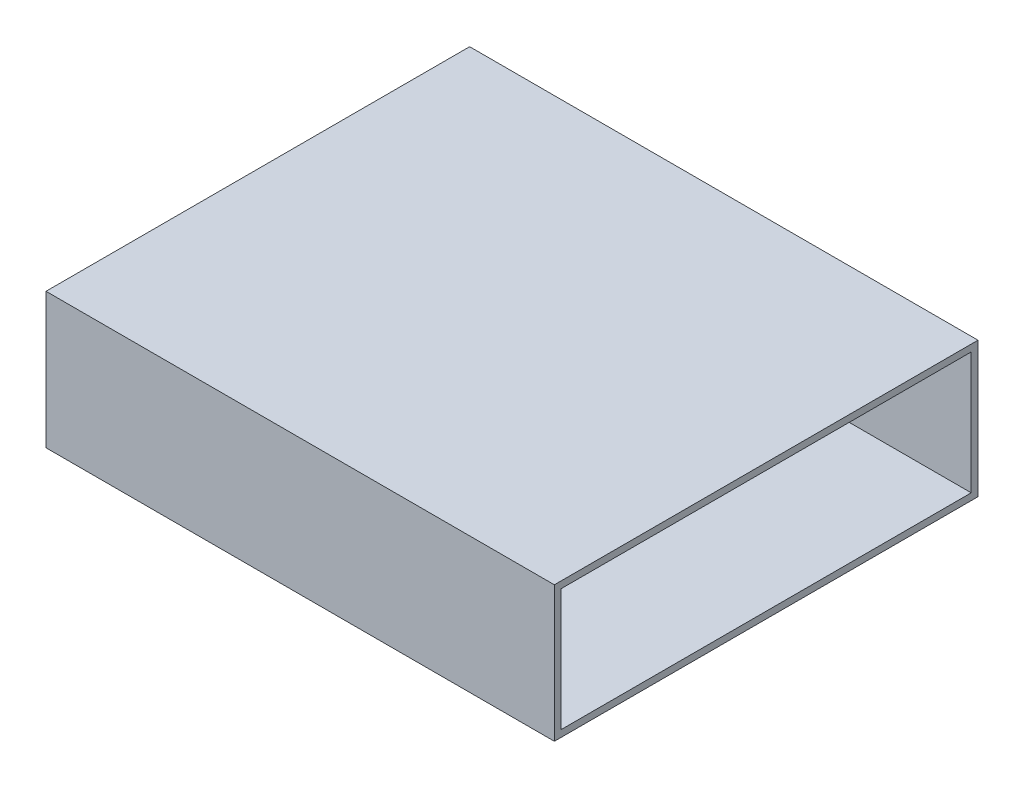
SolidWorks part; units mm, degrees
ref_plane "Front Plane" through (0, 0, 0) normal (0, 0, 1) x (1, 0, 0)
ref_plane "Top Plane" through (0, 0, 0) normal (0, 1, 0) x (1, 0, 0)
ref_plane "Right Plane" through (0, 0, 0) normal (1, 0, 0) x (0, 0, -1)
sketch "Sketch1" plane through (0, 0, 0) normal (1, 0, 0) x (0, 0, -1)
  line L1 (-125, -40) -> (125, -40)
  line L2 (-125, -40) -> (-125, 40)
  line L3 (-125, 40) -> (125, 40)
  line L4 (125, -40) -> (125, 40)
  line L5 (-125, -40) -> (125, 40) construction
  line L6 (-125, 40) -> (125, -40) construction
  line L7 (-121, -36) -> (121, -36)
  line L8 (-121, -36) -> (-121, 36)
  line L9 (-121, 36) -> (121, 36)
  line L10 (121, -36) -> (121, 36)
  line L11 (-121, -36) -> (121, 36) construction
  line L12 (-121, 36) -> (121, -36) construction
  point P0 (0, 0)
  point P6 (0, 0)
  dimension "D1" = 250
  dimension "D2" = 80
  dimension "D3" = 242
  dimension "D4" = 72
extrude "Boss-Extrude1" add sketch "Sketch1" along normal blind 150 and the other way blind 150
